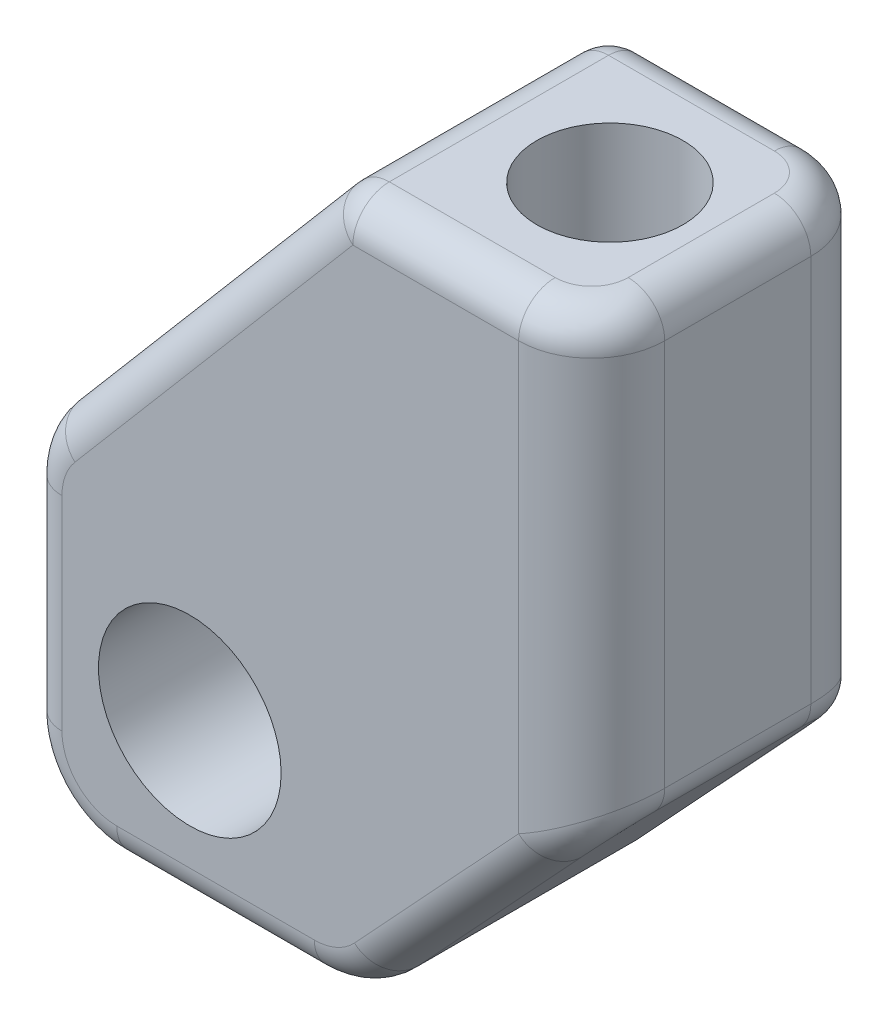
SolidWorks part; units mm, degrees
material "Plain Carbon Steel"
ref_plane "Front Plane" through (0, 0, 0) normal (0, 0, 1) x (1, 0, 0)
ref_plane "Top Plane" through (0, 0, 0) normal (0, 1, 0) x (1, 0, 0)
ref_plane "Right Plane" through (0, 0, 0) normal (1, 0, 0) x (0, 0, -1)
sketch "Sketch1" plane through (0, 0, 0) normal (0, 0, 1) x (1, 0, 0)
  line L0 (10.16, 36.83) -> (27.94, 36.83)
  line L1 (11.43, -11.43) -> (-11.43, -11.43)
  line L4 (-11.43, -11.43) -> (-11.43, 11.43)
  line L5 (11.43, -11.43) -> (-11.43, 11.43) construction
  line L6 (11.43, 11.43) -> (-11.43, -11.43) construction
  line L7 (10.16, 36.83) -> (-11.43, 11.43)
  line L8 (27.94, 36.83) -> (27.94, 6.35)
  line L9 (27.94, 6.35) -> (11.43, -11.43)
  circle A0 centre (0, 0) radius 6.35
  dimension "D1" = 12.7
  dimension "D2" = 22.86
  dimension "D4" = 10.16
  dimension "D5" = 22.86
  dimension "D6" = 27.94
  dimension "D7" = 30.48
  dimension "D8" = 11.43
  dimension "D9" = 25.4
extrude "Boss-Extrude2" add sketch "Sketch1" along normal blind 20.32
sketch "Sketch2" plane through (0, 36.83, 0) normal (0, 1, 0) x (1, 0, 0)
  line L0 (27.94, 0) -> (10.16, 0) construction
  line L1 (10.16, -20.32) -> (10.16, 0) construction
  circle A0 centre (19.05, -10.16) radius 5.08
  dimension "D3" = 10.16
  dimension "D2" = 8.89
  dimension "D1" = 10.16
extrude "Cut-Extrude1" cut sketch "Sketch2" against normal blind 25.4
fillet "Fillet1" radius 5.08 1 edges at (27.94, 21.59, 20.32)
fillet "Fillet2" radius 5.08 1 edges at (27.94, 21.59, 0)
fillet "Fillet3" radius 2.54 1 edges at (10.16, 36.83, 10.16)
fillet "Fillet4" radius 6.35 1 edges at (-11.43, 11.43, 10.16)
fillet "Fillet5" radius 6.35 1 edges at (-11.43, -11.43, 10.16)
fillet "Fillet7" radius 6.35 1 edges at (11.43, -11.43, 10.16)
fillet "Fillet8" radius 2.54 24 edges at (26.4521, 36.83, 18.8321) (17.0973, 36.83, 20.32) (10.2685, 36.5954, 20.32) (-0.2595, 24.5717, 20.32) (-11.0401, 11.2867, 20.32) (-11.43, 2.0079, 20.32) (-9.5701, -9.5701, 20.32) (1.7905, -11.43, 20.32) (11.1992, -10.9007, 20.32) (18.0871, -4.2608, 20.32) (26.4521, 4.7476, 18.8321) (27.94, 6.35, 10.16) (26.4521, 4.7476, 1.4879) (18.0871, -4.2608, 0) (11.1992, -10.9007, 0) (1.7905, -11.43, 0) (-9.5701, -9.5701, 0) (-11.43, 2.0079, 0) (-11.0401, 11.2867, 0) (-0.2595, 24.5717, 0) (10.2685, 36.5954, 0) (17.0973, 36.83, 0) (26.4521, 36.83, 1.4879) (27.94, 36.83, 10.16)
